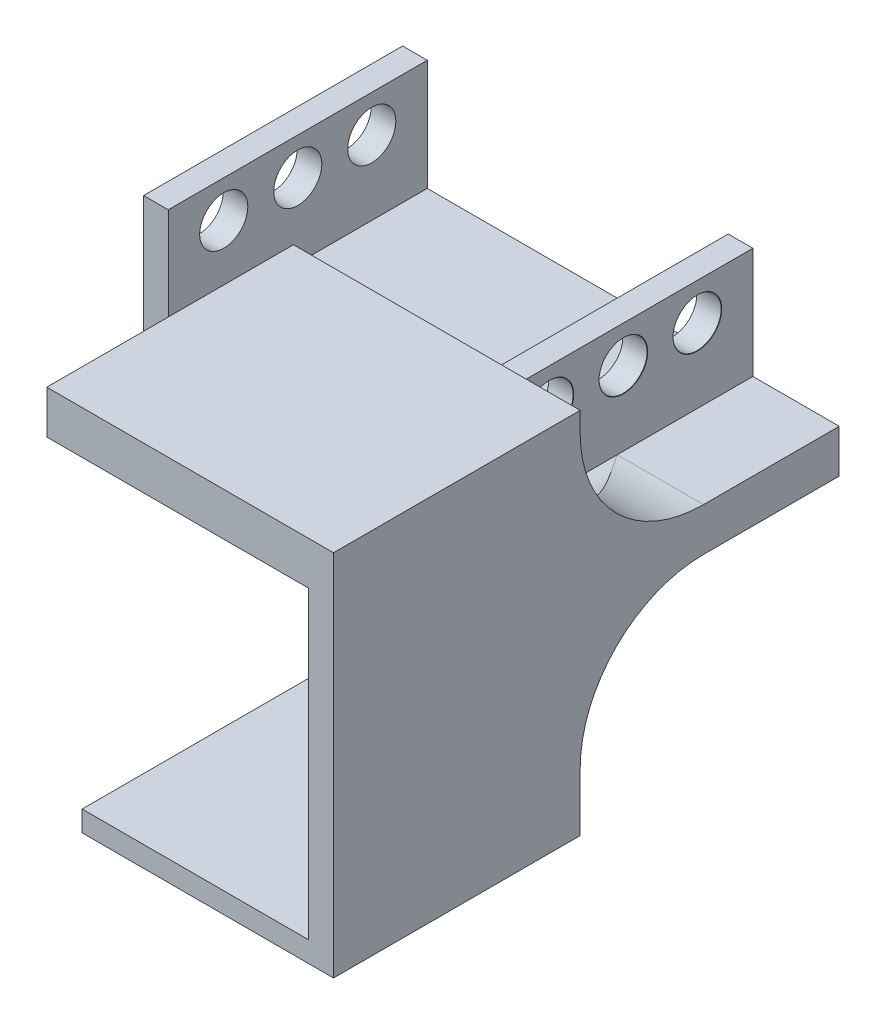
SolidWorks part; units mm, degrees
ref_plane "Front Plane" through (0, 0, 0) normal (0, 0, 1) x (1, 0, 0)
ref_plane "Top Plane" through (0, 0, 0) normal (0, 1, 0) x (1, 0, 0)
ref_plane "Right Plane" through (0, 0, 0) normal (1, 0, 0) x (0, 0, -1)
sketch "Sketch1" plane through (0, 0, 0) normal (0, 0, 1) x (1, 0, 0)
  line L0 (14.421, -30) -> (21.421, -30)
  line L2 (12.421, -21) -> (14.421, -21)
  line L3 (12.421, -21) -> (12.421, -30)
  line L5 (14.421, -21) -> (14.421, -30)
  line L6 (21.421, -33.5) -> (14.421, -33.5)
  line L7 (12.421, -30) -> (-11.979, -30)
  line L12 (-13.979, -33.5) -> (-13.979, -21)
  line L13 (-13.979, -21) -> (-11.979, -21)
  line L14 (-11.979, -30) -> (-11.979, -21)
  line L15 (-11.779, -25.9259) -> (-11.779, -23.0615) construction
  line L16 (14.421, -33.5) -> (-13.979, -33.5)
  line L20 (12.221, -23.0615) -> (12.221, -25.9259) construction
  line L21 (-11.479, -27) -> (-8.779, -27) construction
  line L30 (21.421, -33.5) -> (21.421, -30)
  point P4 (21.4924, -33.5)
  dimension "D1" = 3.5
  dimension "D2" = 2
  dimension "D3" = 2
  dimension "D4" = 0.2
  dimension "D5" = 9
  dimension "D6" = 0.2
  dimension "D7" = 3
extrude "Boss-Extrude1" add sketch "Sketch1" against normal blind 21
hole_wizard "M3.5 Clearance Hole1" positions "Sketch2" profile "Sketch3" hole size "M3.5" standard "ANSI Metric" end condition through all
sketch "Sketch2" plane through (14.421, 0, 0) normal (1, 0, 0) x (0, 0, -1)
  arc A0 (2.5, -24) -> (6.5, -24) centre (4.5, -24) ccw construction
  arc A1 (2.5, -24) -> (6.5, -24) centre (4.5, -24) ccw construction
  arc A2 (8, -24) -> (13, -24) centre (10.5, -24) ccw construction
  arc A3 (8, -24) -> (13, -24) centre (10.5, -24) ccw construction
  arc A4 (8, -24) -> (13, -24) centre (10.5, -24) ccw construction
  arc A5 (8, -24) -> (13, -24) centre (10.5, -24) ccw construction
  arc A6 (14, -24) -> (19, -24) centre (16.5, -24) ccw construction
  arc A7 (14, -24) -> (19, -24) centre (16.5, -24) ccw construction
  point P0 (4.5, -24)
  point P2 (10.5, -24)
  point P4 (16.5, -24)
sketch "Sketch3" plane through (14.421, -24, -4.5) normal (0, 1, 0) x (0, 0, -1)
  line L0 (0, 0) -> (0, 28.4)
  line L1 (0, 28.4) -> (1.95, 28.4)
  line L2 (1.95, 28.4) -> (1.95, 0.025)
  line L3 (1.95, 0.025) -> (1.975, 0)
  line L5 (1.975, 0) -> (0, 0)
  line L6 (-1.95, 0.025) -> (-1.975, 0) construction
  line L11 (0, -6.35) -> (0, 107.95) construction
  dimension "Thru Hole Dia." = 3.9
  dimension "Thru Hole Depth" = 28.4
  dimension "Near C'Sink Dia." = 3.95
  dimension "Near C'Sink Angle" = 90
sketch "Sketch4" plane through (0, -33.5, 0) normal (0, -1, 0) x (1, 0, 0)
  line L14 (14.421, -21) -> (14.421, 0) construction
  circle A7 centre (1.421, -10.5) radius 9
  circle A8 centre (1.421, -10.5) radius 6 construction
  circle A9 centre (1.421, -4.5) radius 2
  circle A10 centre (1.421, -16.5) radius 2
  circle A11 centre (-4.579, -10.5) radius 2
  circle A12 centre (7.421, -10.5) radius 2
  dimension "D5" = 18
  dimension "D6" = 12
  dimension "D7" = 4
  dimension "D8" = 4
  dimension "D9" = 4
  dimension "D10" = 4
  dimension "D2" = 13
extrude "Cut-Extrude1" cut sketch "Sketch4" against normal blind 3
sketch "Sketch8" plane through (0, 0, 0) normal (0, 0, 1) x (1, 0, 0)
  line L1 (21.421, -48.2391) -> (1.0389, -48.2391)
  line L3 (19.3885, -46.5659) -> (1.0389, -46.5659)
  line L4 (1.0389, -48.2391) -> (1.0389, -46.5659)
  line L8 (21.421, -48.2391) -> (21.421, -18.3794)
  line L10 (19.3885, -46.5659) -> (19.3885, -21.8794)
  line L11 (21.421, -18.3794) -> (-1.8281, -18.3794)
  line L13 (19.3885, -21.8794) -> (-1.8281, -21.8794)
  line L14 (-1.8281, -18.3794) -> (-1.8281, -21.8794)
  point P8 (21.421, -40.368)
  point P12 (21.5505, -20.0205)
  dimension "D1" = 3.5
extrude "Boss-Extrude2" add sketch "Sketch8" along normal blind 20 contours L10 L13 L14 L11 L8 L1 L4 L3
sketch "Sketch9" plane through (0, -21.8794, 0) normal (0, -1, 0) x (1, 0, 0)
  line L0 (21.421, 10) -> (-55.3921, 10) construction
  line L1 (21.421, 20) -> (21.421, 0) construction
  circle A0 centre (8.421, 10) radius 9
  circle A1 centre (8.421, 10) radius 6 construction
  circle A2 centre (8.421, 16) radius 2
  circle A3 centre (8.421, 4) radius 2
  circle A4 centre (2.421, 10) radius 2
  circle A5 centre (14.421, 10) radius 2
  point P15 (7.3391, 10)
  dimension "D1" = 18
  dimension "D2" = 12
  dimension "D3" = 4
  dimension "D4" = 4
  dimension "D5" = 4
  dimension "D6" = 4
  dimension "D7" = 13
ref_plane "Plane1" through (19.3885, -30, 0) normal (0, 1, 0) x (1, 0, 0)
fillet "Fillet1" radius 10 2 edges at (20.4047, -30, 0) (20.4047, -33.5, 0)
fillet "Fillet2" radius 5 1 edges at (19.3885, -31.75, 0)
fillet "Fillet3" radius 5 2 edges at (19.3885, -30, -2.5) (19.3885, -33.5, -2.5)
fillet "Fillet4" radius 2 2 edges at (14.4047, -21.8794, 0) (13.4047, -21.8794, 0)
extrude "Cut-Extrude2" cut sketch "Sketch9" against normal blind 3
